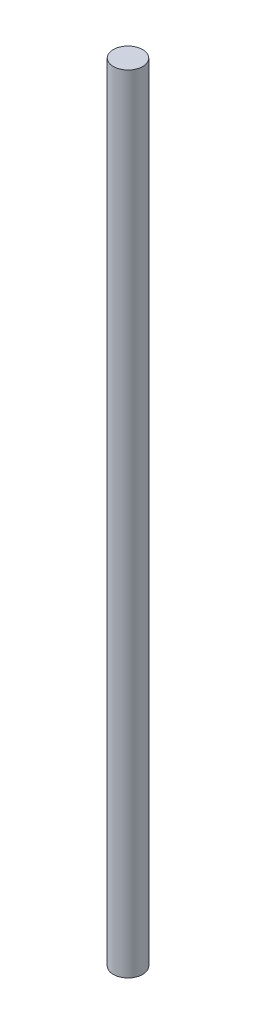
SolidWorks part; units mm, degrees
material "ALUMINUM 6061-T6"
ref_plane "Front Plane" through (0, 0, 0) normal (0, 0, 1) x (1, 0, 0)
ref_plane "Top Plane" through (0, 0, 0) normal (0, 1, 0) x (1, 0, 0)
ref_plane "Right Plane" through (0, 0, 0) normal (1, 0, 0) x (0, 0, -1)
sketch "Sketch1" plane through (0, 0, 0) normal (0, 1, 0) x (1, 0, 0)
  circle A0 centre (0, 0) radius 9.4996
extrude "Boss-Extrude1" add sketch "Sketch1" along normal mid plane 508
